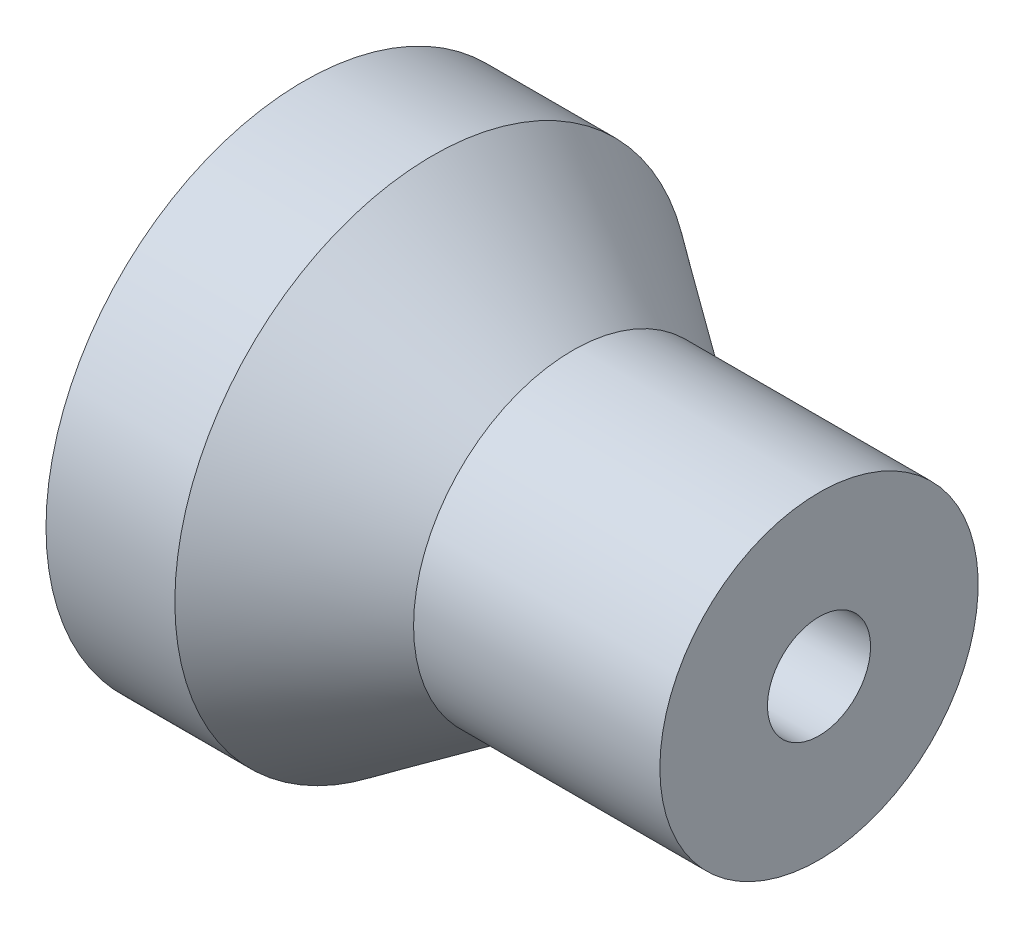
SolidWorks part; units mm, degrees
ref_plane "Front Plane" through (0, 0, 0) normal (0, 0, 1) x (1, 0, 0)
ref_plane "Top Plane" through (0, 0, 0) normal (0, 1, 0) x (1, 0, 0)
ref_plane "Right Plane" through (0, 0, 0) normal (1, 0, 0) x (0, 0, -1)
sketch "Sketch1" plane through (0, 0, 0) normal (0, 1, 0) x (1, 0, 0)
  line L0 (-68.0882, 0) -> (68.9706, 0) construction
  line L1 (-30.1471, 0) -> (-30.1471, 10)
  line L2 (-30.1471, 10) -> (-25.1471, 10)
  line L3 (-25.1471, 10) -> (-19.7059, 6.1765)
  line L4 (-19.7059, 6.1765) -> (-10.1471, 6.1765)
  line L5 (-10.1471, 6.1765) -> (-10.1471, 0)
  line L6 (-10.1471, 0) -> (-30.1471, 0)
  dimension "D1" = 10
  dimension "D2" = 15
  dimension "D3" = 5
revolve "Revolve1" add sketch "Sketch1" angle 360 about L0
sketch "Sketch2" plane through (-10.1471, 0, 0) normal (1, 0, 0) x (0, 0, -1)
  circle A0 centre (0, 0) radius 2
extrude "Cut-Extrude2" cut sketch "Sketch2" against normal blind 18
sketch "Sketch3" plane through (-30.1471, 0, 0) normal (-1, 0, 0) x (0, 0, 1)
  circle A0 centre (0, 0) radius 4.5
extrude "Cut-Extrude3" cut sketch "Sketch3" against normal blind 2
chamfer "Chamfer2" distance 3 angle 45 1 edges at (-28.1471, 0, -2)
